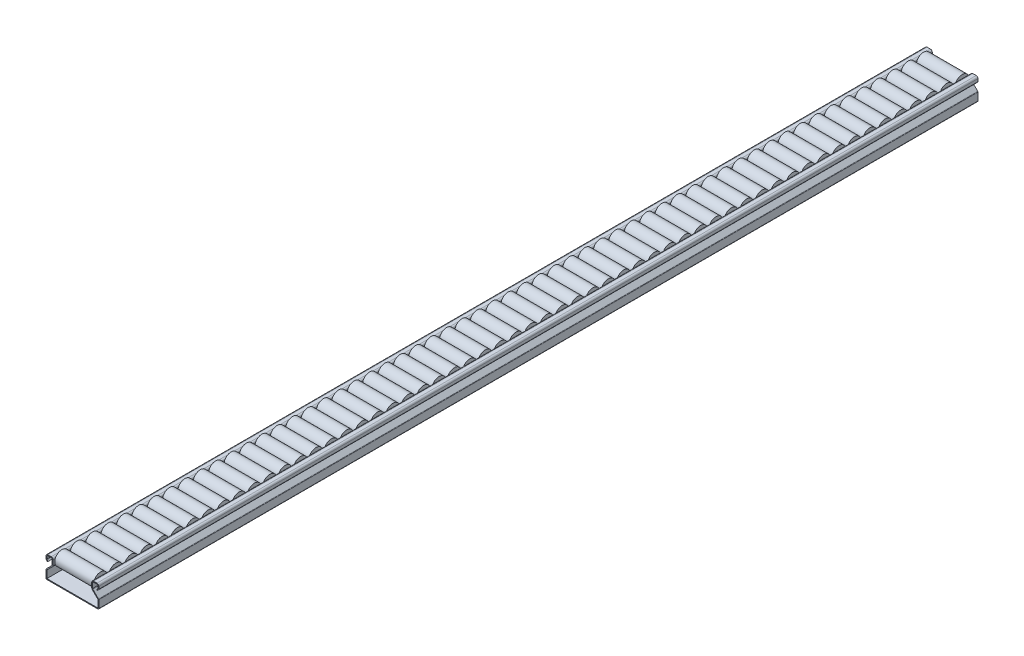
SolidWorks part; units mm, degrees
ref_plane "Front Plane" through (0, 0, 0) normal (0, 0, 1) x (1, 0, 0)
ref_plane "Top Plane" through (0, 0, 0) normal (0, 1, 0) x (1, 0, 0)
ref_plane "Right Plane" through (0, 0, 0) normal (1, 0, 0) x (0, 0, -1)
ref_plane "Plane1" through (0, 0, 1000) normal (0, 0, 1) x (1, 0, 0)
sketch "Sketch1" plane through (0, 0, 1000) normal (0, 0, 1) x (1, 0, 0)
  line L0 (30, 0) -> (30, 25)
  line L1 (30, 25) -> (24, 25)
  line L2 (22, 23) -> (22, 17.4142)
  line L3 (22.5858, 16) -> (29, 9.5858)
  line L4 (29, 9.5858) -> (29, 1)
  line L5 (29, 1) -> (-29, 1)
  line L6 (-29, 1) -> (-29, 9.5858)
  line L7 (-29, 9.5858) -> (-22.5858, 16)
  line L8 (-22, 17.4142) -> (-22, 23)
  line L9 (-24, 25) -> (-30, 25)
  line L10 (-30, 25) -> (-30, 0)
  line L11 (-30, 0) -> (30, 0)
  arc A0 (24, 25) -> (22, 23) centre (24, 23) ccw
  arc A1 (22, 17.4142) -> (22.5858, 16) centre (24, 17.4142) ccw
  arc A2 (-22.5858, 16) -> (-22, 17.4142) centre (-24, 17.4142) ccw
  arc A3 (-22, 23) -> (-24, 25) centre (-24, 23) ccw
extrude "Boss-Extrude1" add sketch "Sketch1" against normal blind 1000
sketch "Sketch2" plane through (0, 0, 0) normal (0, 0, -1) x (-1, 0, 0)
  line L0 (30, 10) -> (30, 19.5858)
  line L1 (30, 19.5858) -> (28.2929, 17.8787)
  line L2 (28.2929, 17.8787) -> (27.5858, 18.5858)
  line L3 (27.5858, 18.5858) -> (29, 20)
  line L4 (29, 20) -> (29, 24)
  line L5 (29, 24) -> (23, 24)
  line L6 (23, 24) -> (23, 17)
  line L7 (23, 17) -> (30, 10)
extrude "Cut-Extrude1" cut sketch "Sketch2" against normal through all
sketch "Sketch3" plane through (0, 0, 0) normal (0, 0, -1) x (-1, 0, 0)
  line L0 (-30, 19.5858) -> (-30, 10)
  line L1 (-30, 10) -> (-23, 17)
  line L2 (-23, 17) -> (-23, 24)
  line L3 (-23, 24) -> (-29, 24)
  line L4 (-29, 24) -> (-29, 20)
  line L5 (-29, 20) -> (-27.5858, 18.5858)
  line L6 (-27.5858, 18.5858) -> (-28.2929, 17.8787)
  line L7 (-28.2929, 17.8787) -> (-30, 19.5858)
extrude "Cut-Extrude2" cut sketch "Sketch3" against normal through all
ref_plane "Plane2" through (0, 0, 10) normal (0, 0, -1) x (-1, 0, 0)
sketch "Sketch4" plane through (0, 0, 10) normal (0, 0, -1) x (-1, 0, 0)
  line L0 (-22, 28) -> (-22, 20)
  line L1 (-22, 20) -> (22, 20)
  line L2 (22, 20) -> (22, 28)
  line L3 (22, 28) -> (-22, 28)
  line L4 (-22, 20) -> (22, 20) construction
revolve "Revolve1" add sketch "Sketch4" angle 360 about L4 reverse direction yes
ref_plane "Plane3" through (0, 0, 990) normal (0, 0, -1) x (-1, 0, 0)
sketch "Sketch5" plane through (0, 0, 990) normal (0, 0, -1) x (-1, 0, 0)
  line L0 (-22, 28) -> (-22, 20)
  line L1 (-22, 20) -> (22, 20)
  line L2 (22, 20) -> (22, 28)
  line L3 (22, 28) -> (-22, 28)
  line L4 (-22, 20) -> (22, 20) construction
revolve "Revolve2" add sketch "Sketch5" angle 360 about L4 reverse direction yes
ref_plane "Plane4" through (0, 0, 27.5) normal (0, 0, -1) x (-1, 0, 0)
sketch "Sketch6" plane through (0, 0, 27.5) normal (0, 0, -1) x (-1, 0, 0)
  line L0 (-22, 28) -> (-22, 20)
  line L1 (-22, 20) -> (22, 20)
  line L2 (22, 20) -> (22, 28)
  line L3 (22, 28) -> (-22, 28)
  line L4 (-22, 20) -> (22, 20) construction
revolve "Revolve3" add sketch "Sketch6" angle 360 about L4 reverse direction yes
ref_plane "Plane5" through (0, 0, 45) normal (0, 0, -1) x (-1, 0, 0)
sketch "Sketch7" plane through (0, 0, 45) normal (0, 0, -1) x (-1, 0, 0)
  line L0 (-22, 28) -> (-22, 20)
  line L1 (-22, 20) -> (22, 20)
  line L2 (22, 20) -> (22, 28)
  line L3 (22, 28) -> (-22, 28)
  line L4 (-22, 20) -> (22, 20) construction
revolve "Revolve4" add sketch "Sketch7" angle 360 about L4 reverse direction yes
ref_plane "Plane6" through (0, 0, 62.5) normal (0, 0, -1) x (-1, 0, 0)
sketch "Sketch8" plane through (0, 0, 62.5) normal (0, 0, -1) x (-1, 0, 0)
  line L0 (-22, 28) -> (-22, 20)
  line L1 (-22, 20) -> (22, 20)
  line L2 (22, 20) -> (22, 28)
  line L3 (22, 28) -> (-22, 28)
  line L4 (-22, 20) -> (22, 20) construction
revolve "Revolve5" add sketch "Sketch8" angle 360 about L4 reverse direction yes
ref_plane "Plane7" through (0, 0, 80) normal (0, 0, -1) x (-1, 0, 0)
sketch "Sketch9" plane through (0, 0, 80) normal (0, 0, -1) x (-1, 0, 0)
  line L0 (-22, 28) -> (-22, 20)
  line L1 (-22, 20) -> (22, 20)
  line L2 (22, 20) -> (22, 28)
  line L3 (22, 28) -> (-22, 28)
  line L4 (-22, 20) -> (22, 20) construction
revolve "Revolve6" add sketch "Sketch9" angle 360 about L4 reverse direction yes
ref_plane "Plane8" through (0, 0, 97.5) normal (0, 0, -1) x (-1, 0, 0)
sketch "Sketch10" plane through (0, 0, 97.5) normal (0, 0, -1) x (-1, 0, 0)
  line L0 (-22, 28) -> (-22, 20)
  line L1 (-22, 20) -> (22, 20)
  line L2 (22, 20) -> (22, 28)
  line L3 (22, 28) -> (-22, 28)
  line L4 (-22, 20) -> (22, 20) construction
revolve "Revolve7" add sketch "Sketch10" angle 360 about L4 reverse direction yes
ref_plane "Plane9" through (0, 0, 115) normal (0, 0, -1) x (-1, 0, 0)
sketch "Sketch11" plane through (0, 0, 115) normal (0, 0, -1) x (-1, 0, 0)
  line L0 (-22, 28) -> (-22, 20)
  line L1 (-22, 20) -> (22, 20)
  line L2 (22, 20) -> (22, 28)
  line L3 (22, 28) -> (-22, 28)
  line L4 (-22, 20) -> (22, 20) construction
revolve "Revolve8" add sketch "Sketch11" angle 360 about L4 reverse direction yes
ref_plane "Plane10" through (0, 0, 132.5) normal (0, 0, -1) x (-1, 0, 0)
sketch "Sketch12" plane through (0, 0, 132.5) normal (0, 0, -1) x (-1, 0, 0)
  line L0 (-22, 28) -> (-22, 20)
  line L1 (-22, 20) -> (22, 20)
  line L2 (22, 20) -> (22, 28)
  line L3 (22, 28) -> (-22, 28)
  line L4 (-22, 20) -> (22, 20) construction
revolve "Revolve9" add sketch "Sketch12" angle 360 about L4 reverse direction yes
ref_plane "Plane11" through (0, 0, 150) normal (0, 0, -1) x (-1, 0, 0)
sketch "Sketch13" plane through (0, 0, 150) normal (0, 0, -1) x (-1, 0, 0)
  line L0 (-22, 28) -> (-22, 20)
  line L1 (-22, 20) -> (22, 20)
  line L2 (22, 20) -> (22, 28)
  line L3 (22, 28) -> (-22, 28)
  line L4 (-22, 20) -> (22, 20) construction
revolve "Revolve10" add sketch "Sketch13" angle 360 about L4 reverse direction yes
ref_plane "Plane12" through (0, 0, 167.5) normal (0, 0, -1) x (-1, 0, 0)
sketch "Sketch14" plane through (0, 0, 167.5) normal (0, 0, -1) x (-1, 0, 0)
  line L0 (-22, 28) -> (-22, 20)
  line L1 (-22, 20) -> (22, 20)
  line L2 (22, 20) -> (22, 28)
  line L3 (22, 28) -> (-22, 28)
  line L4 (-22, 20) -> (22, 20) construction
revolve "Revolve11" add sketch "Sketch14" angle 360 about L4 reverse direction yes
ref_plane "Plane13" through (0, 0, 185) normal (0, 0, -1) x (-1, 0, 0)
sketch "Sketch15" plane through (0, 0, 185) normal (0, 0, -1) x (-1, 0, 0)
  line L0 (-22, 28) -> (-22, 20)
  line L1 (-22, 20) -> (22, 20)
  line L2 (22, 20) -> (22, 28)
  line L3 (22, 28) -> (-22, 28)
  line L4 (-22, 20) -> (22, 20) construction
revolve "Revolve12" add sketch "Sketch15" angle 360 about L4 reverse direction yes
ref_plane "Plane14" through (0, 0, 202.5) normal (0, 0, -1) x (-1, 0, 0)
sketch "Sketch16" plane through (0, 0, 202.5) normal (0, 0, -1) x (-1, 0, 0)
  line L0 (-22, 28) -> (-22, 20)
  line L1 (-22, 20) -> (22, 20)
  line L2 (22, 20) -> (22, 28)
  line L3 (22, 28) -> (-22, 28)
  line L4 (-22, 20) -> (22, 20) construction
revolve "Revolve13" add sketch "Sketch16" angle 360 about L4 reverse direction yes
ref_plane "Plane15" through (0, 0, 220) normal (0, 0, -1) x (-1, 0, 0)
sketch "Sketch17" plane through (0, 0, 220) normal (0, 0, -1) x (-1, 0, 0)
  line L0 (-22, 28) -> (-22, 20)
  line L1 (-22, 20) -> (22, 20)
  line L2 (22, 20) -> (22, 28)
  line L3 (22, 28) -> (-22, 28)
  line L4 (-22, 20) -> (22, 20) construction
revolve "Revolve14" add sketch "Sketch17" angle 360 about L4 reverse direction yes
ref_plane "Plane16" through (0, 0, 237.5) normal (0, 0, -1) x (-1, 0, 0)
sketch "Sketch18" plane through (0, 0, 237.5) normal (0, 0, -1) x (-1, 0, 0)
  line L0 (-22, 28) -> (-22, 20)
  line L1 (-22, 20) -> (22, 20)
  line L2 (22, 20) -> (22, 28)
  line L3 (22, 28) -> (-22, 28)
  line L4 (-22, 20) -> (22, 20) construction
revolve "Revolve15" add sketch "Sketch18" angle 360 about L4 reverse direction yes
ref_plane "Plane17" through (0, 0, 255) normal (0, 0, -1) x (-1, 0, 0)
sketch "Sketch19" plane through (0, 0, 255) normal (0, 0, -1) x (-1, 0, 0)
  line L0 (-22, 28) -> (-22, 20)
  line L1 (-22, 20) -> (22, 20)
  line L2 (22, 20) -> (22, 28)
  line L3 (22, 28) -> (-22, 28)
  line L4 (-22, 20) -> (22, 20) construction
revolve "Revolve16" add sketch "Sketch19" angle 360 about L4 reverse direction yes
ref_plane "Plane18" through (0, 0, 272.5) normal (0, 0, -1) x (-1, 0, 0)
sketch "Sketch20" plane through (0, 0, 272.5) normal (0, 0, -1) x (-1, 0, 0)
  line L0 (-22, 28) -> (-22, 20)
  line L1 (-22, 20) -> (22, 20)
  line L2 (22, 20) -> (22, 28)
  line L3 (22, 28) -> (-22, 28)
  line L4 (-22, 20) -> (22, 20) construction
revolve "Revolve17" add sketch "Sketch20" angle 360 about L4 reverse direction yes
ref_plane "Plane19" through (0, 0, 290) normal (0, 0, -1) x (-1, 0, 0)
sketch "Sketch21" plane through (0, 0, 290) normal (0, 0, -1) x (-1, 0, 0)
  line L0 (-22, 28) -> (-22, 20)
  line L1 (-22, 20) -> (22, 20)
  line L2 (22, 20) -> (22, 28)
  line L3 (22, 28) -> (-22, 28)
  line L4 (-22, 20) -> (22, 20) construction
revolve "Revolve18" add sketch "Sketch21" angle 360 about L4 reverse direction yes
ref_plane "Plane20" through (0, 0, 307.5) normal (0, 0, -1) x (-1, 0, 0)
sketch "Sketch22" plane through (0, 0, 307.5) normal (0, 0, -1) x (-1, 0, 0)
  line L0 (-22, 28) -> (-22, 20)
  line L1 (-22, 20) -> (22, 20)
  line L2 (22, 20) -> (22, 28)
  line L3 (22, 28) -> (-22, 28)
  line L4 (-22, 20) -> (22, 20) construction
revolve "Revolve19" add sketch "Sketch22" angle 360 about L4 reverse direction yes
ref_plane "Plane21" through (0, 0, 325) normal (0, 0, -1) x (-1, 0, 0)
sketch "Sketch23" plane through (0, 0, 325) normal (0, 0, -1) x (-1, 0, 0)
  line L0 (-22, 28) -> (-22, 20)
  line L1 (-22, 20) -> (22, 20)
  line L2 (22, 20) -> (22, 28)
  line L3 (22, 28) -> (-22, 28)
  line L4 (-22, 20) -> (22, 20) construction
revolve "Revolve20" add sketch "Sketch23" angle 360 about L4 reverse direction yes
ref_plane "Plane22" through (0, 0, 342.5) normal (0, 0, -1) x (-1, 0, 0)
sketch "Sketch24" plane through (0, 0, 342.5) normal (0, 0, -1) x (-1, 0, 0)
  line L0 (-22, 28) -> (-22, 20)
  line L1 (-22, 20) -> (22, 20)
  line L2 (22, 20) -> (22, 28)
  line L3 (22, 28) -> (-22, 28)
  line L4 (-22, 20) -> (22, 20) construction
revolve "Revolve21" add sketch "Sketch24" angle 360 about L4 reverse direction yes
ref_plane "Plane23" through (0, 0, 360) normal (0, 0, -1) x (-1, 0, 0)
sketch "Sketch25" plane through (0, 0, 360) normal (0, 0, -1) x (-1, 0, 0)
  line L0 (-22, 28) -> (-22, 20)
  line L1 (-22, 20) -> (22, 20)
  line L2 (22, 20) -> (22, 28)
  line L3 (22, 28) -> (-22, 28)
  line L4 (-22, 20) -> (22, 20) construction
revolve "Revolve22" add sketch "Sketch25" angle 360 about L4 reverse direction yes
ref_plane "Plane24" through (0, 0, 377.5) normal (0, 0, -1) x (-1, 0, 0)
sketch "Sketch26" plane through (0, 0, 377.5) normal (0, 0, -1) x (-1, 0, 0)
  line L0 (-22, 28) -> (-22, 20)
  line L1 (-22, 20) -> (22, 20)
  line L2 (22, 20) -> (22, 28)
  line L3 (22, 28) -> (-22, 28)
  line L4 (-22, 20) -> (22, 20) construction
revolve "Revolve23" add sketch "Sketch26" angle 360 about L4 reverse direction yes
ref_plane "Plane25" through (0, 0, 395) normal (0, 0, -1) x (-1, 0, 0)
sketch "Sketch27" plane through (0, 0, 395) normal (0, 0, -1) x (-1, 0, 0)
  line L0 (-22, 28) -> (-22, 20)
  line L1 (-22, 20) -> (22, 20)
  line L2 (22, 20) -> (22, 28)
  line L3 (22, 28) -> (-22, 28)
  line L4 (-22, 20) -> (22, 20) construction
revolve "Revolve24" add sketch "Sketch27" angle 360 about L4 reverse direction yes
ref_plane "Plane26" through (0, 0, 412.5) normal (0, 0, -1) x (-1, 0, 0)
sketch "Sketch28" plane through (0, 0, 412.5) normal (0, 0, -1) x (-1, 0, 0)
  line L0 (-22, 28) -> (-22, 20)
  line L1 (-22, 20) -> (22, 20)
  line L2 (22, 20) -> (22, 28)
  line L3 (22, 28) -> (-22, 28)
  line L4 (-22, 20) -> (22, 20) construction
revolve "Revolve25" add sketch "Sketch28" angle 360 about L4 reverse direction yes
ref_plane "Plane27" through (0, 0, 430) normal (0, 0, -1) x (-1, 0, 0)
sketch "Sketch29" plane through (0, 0, 430) normal (0, 0, -1) x (-1, 0, 0)
  line L0 (-22, 28) -> (-22, 20)
  line L1 (-22, 20) -> (22, 20)
  line L2 (22, 20) -> (22, 28)
  line L3 (22, 28) -> (-22, 28)
  line L4 (-22, 20) -> (22, 20) construction
revolve "Revolve26" add sketch "Sketch29" angle 360 about L4 reverse direction yes
ref_plane "Plane28" through (0, 0, 447.5) normal (0, 0, -1) x (-1, 0, 0)
sketch "Sketch30" plane through (0, 0, 447.5) normal (0, 0, -1) x (-1, 0, 0)
  line L0 (-22, 28) -> (-22, 20)
  line L1 (-22, 20) -> (22, 20)
  line L2 (22, 20) -> (22, 28)
  line L3 (22, 28) -> (-22, 28)
  line L4 (-22, 20) -> (22, 20) construction
revolve "Revolve27" add sketch "Sketch30" angle 360 about L4 reverse direction yes
ref_plane "Plane29" through (0, 0, 465) normal (0, 0, -1) x (-1, 0, 0)
sketch "Sketch31" plane through (0, 0, 465) normal (0, 0, -1) x (-1, 0, 0)
  line L0 (-22, 28) -> (-22, 20)
  line L1 (-22, 20) -> (22, 20)
  line L2 (22, 20) -> (22, 28)
  line L3 (22, 28) -> (-22, 28)
  line L4 (-22, 20) -> (22, 20) construction
revolve "Revolve28" add sketch "Sketch31" angle 360 about L4 reverse direction yes
ref_plane "Plane30" through (0, 0, 482.5) normal (0, 0, -1) x (-1, 0, 0)
sketch "Sketch32" plane through (0, 0, 482.5) normal (0, 0, -1) x (-1, 0, 0)
  line L0 (-22, 28) -> (-22, 20)
  line L1 (-22, 20) -> (22, 20)
  line L2 (22, 20) -> (22, 28)
  line L3 (22, 28) -> (-22, 28)
  line L4 (-22, 20) -> (22, 20) construction
revolve "Revolve29" add sketch "Sketch32" angle 360 about L4 reverse direction yes
ref_plane "Plane31" through (0, 0, 500) normal (0, 0, -1) x (-1, 0, 0)
sketch "Sketch33" plane through (0, 0, 500) normal (0, 0, -1) x (-1, 0, 0)
  line L0 (-22, 28) -> (-22, 20)
  line L1 (-22, 20) -> (22, 20)
  line L2 (22, 20) -> (22, 28)
  line L3 (22, 28) -> (-22, 28)
  line L4 (-22, 20) -> (22, 20) construction
revolve "Revolve30" add sketch "Sketch33" angle 360 about L4 reverse direction yes
ref_plane "Plane32" through (0, 0, 517.5) normal (0, 0, -1) x (-1, 0, 0)
sketch "Sketch34" plane through (0, 0, 517.5) normal (0, 0, -1) x (-1, 0, 0)
  line L0 (-22, 28) -> (-22, 20)
  line L1 (-22, 20) -> (22, 20)
  line L2 (22, 20) -> (22, 28)
  line L3 (22, 28) -> (-22, 28)
  line L4 (-22, 20) -> (22, 20) construction
revolve "Revolve31" add sketch "Sketch34" angle 360 about L4 reverse direction yes
ref_plane "Plane33" through (0, 0, 535) normal (0, 0, -1) x (-1, 0, 0)
sketch "Sketch35" plane through (0, 0, 535) normal (0, 0, -1) x (-1, 0, 0)
  line L0 (-22, 28) -> (-22, 20)
  line L1 (-22, 20) -> (22, 20)
  line L2 (22, 20) -> (22, 28)
  line L3 (22, 28) -> (-22, 28)
  line L4 (-22, 20) -> (22, 20) construction
revolve "Revolve32" add sketch "Sketch35" angle 360 about L4 reverse direction yes
ref_plane "Plane34" through (0, 0, 552.5) normal (0, 0, -1) x (-1, 0, 0)
sketch "Sketch36" plane through (0, 0, 552.5) normal (0, 0, -1) x (-1, 0, 0)
  line L0 (-22, 28) -> (-22, 20)
  line L1 (-22, 20) -> (22, 20)
  line L2 (22, 20) -> (22, 28)
  line L3 (22, 28) -> (-22, 28)
  line L4 (-22, 20) -> (22, 20) construction
revolve "Revolve33" add sketch "Sketch36" angle 360 about L4 reverse direction yes
ref_plane "Plane35" through (0, 0, 570) normal (0, 0, -1) x (-1, 0, 0)
sketch "Sketch37" plane through (0, 0, 570) normal (0, 0, -1) x (-1, 0, 0)
  line L0 (-22, 28) -> (-22, 20)
  line L1 (-22, 20) -> (22, 20)
  line L2 (22, 20) -> (22, 28)
  line L3 (22, 28) -> (-22, 28)
  line L4 (-22, 20) -> (22, 20) construction
revolve "Revolve34" add sketch "Sketch37" angle 360 about L4 reverse direction yes
ref_plane "Plane36" through (0, 0, 587.5) normal (0, 0, -1) x (-1, 0, 0)
sketch "Sketch38" plane through (0, 0, 587.5) normal (0, 0, -1) x (-1, 0, 0)
  line L0 (-22, 28) -> (-22, 20)
  line L1 (-22, 20) -> (22, 20)
  line L2 (22, 20) -> (22, 28)
  line L3 (22, 28) -> (-22, 28)
  line L4 (-22, 20) -> (22, 20) construction
revolve "Revolve35" add sketch "Sketch38" angle 360 about L4 reverse direction yes
ref_plane "Plane37" through (0, 0, 605) normal (0, 0, -1) x (-1, 0, 0)
sketch "Sketch39" plane through (0, 0, 605) normal (0, 0, -1) x (-1, 0, 0)
  line L0 (-22, 28) -> (-22, 20)
  line L1 (-22, 20) -> (22, 20)
  line L2 (22, 20) -> (22, 28)
  line L3 (22, 28) -> (-22, 28)
  line L4 (-22, 20) -> (22, 20) construction
revolve "Revolve36" add sketch "Sketch39" angle 360 about L4 reverse direction yes
ref_plane "Plane38" through (0, 0, 622.5) normal (0, 0, -1) x (-1, 0, 0)
sketch "Sketch40" plane through (0, 0, 622.5) normal (0, 0, -1) x (-1, 0, 0)
  line L0 (-22, 28) -> (-22, 20)
  line L1 (-22, 20) -> (22, 20)
  line L2 (22, 20) -> (22, 28)
  line L3 (22, 28) -> (-22, 28)
  line L4 (-22, 20) -> (22, 20) construction
revolve "Revolve37" add sketch "Sketch40" angle 360 about L4 reverse direction yes
ref_plane "Plane39" through (0, 0, 640) normal (0, 0, -1) x (-1, 0, 0)
sketch "Sketch41" plane through (0, 0, 640) normal (0, 0, -1) x (-1, 0, 0)
  line L0 (-22, 28) -> (-22, 20)
  line L1 (-22, 20) -> (22, 20)
  line L2 (22, 20) -> (22, 28)
  line L3 (22, 28) -> (-22, 28)
  line L4 (-22, 20) -> (22, 20) construction
revolve "Revolve38" add sketch "Sketch41" angle 360 about L4 reverse direction yes
ref_plane "Plane40" through (0, 0, 657.5) normal (0, 0, -1) x (-1, 0, 0)
sketch "Sketch42" plane through (0, 0, 657.5) normal (0, 0, -1) x (-1, 0, 0)
  line L0 (-22, 28) -> (-22, 20)
  line L1 (-22, 20) -> (22, 20)
  line L2 (22, 20) -> (22, 28)
  line L3 (22, 28) -> (-22, 28)
  line L4 (-22, 20) -> (22, 20) construction
revolve "Revolve39" add sketch "Sketch42" angle 360 about L4 reverse direction yes
ref_plane "Plane41" through (0, 0, 675) normal (0, 0, -1) x (-1, 0, 0)
sketch "Sketch43" plane through (0, 0, 675) normal (0, 0, -1) x (-1, 0, 0)
  line L0 (-22, 28) -> (-22, 20)
  line L1 (-22, 20) -> (22, 20)
  line L2 (22, 20) -> (22, 28)
  line L3 (22, 28) -> (-22, 28)
  line L4 (-22, 20) -> (22, 20) construction
revolve "Revolve40" add sketch "Sketch43" angle 360 about L4 reverse direction yes
ref_plane "Plane42" through (0, 0, 692.5) normal (0, 0, -1) x (-1, 0, 0)
sketch "Sketch44" plane through (0, 0, 692.5) normal (0, 0, -1) x (-1, 0, 0)
  line L0 (-22, 28) -> (-22, 20)
  line L1 (-22, 20) -> (22, 20)
  line L2 (22, 20) -> (22, 28)
  line L3 (22, 28) -> (-22, 28)
  line L4 (-22, 20) -> (22, 20) construction
revolve "Revolve41" add sketch "Sketch44" angle 360 about L4 reverse direction yes
ref_plane "Plane43" through (0, 0, 710) normal (0, 0, -1) x (-1, 0, 0)
sketch "Sketch45" plane through (0, 0, 710) normal (0, 0, -1) x (-1, 0, 0)
  line L0 (-22, 28) -> (-22, 20)
  line L1 (-22, 20) -> (22, 20)
  line L2 (22, 20) -> (22, 28)
  line L3 (22, 28) -> (-22, 28)
  line L4 (-22, 20) -> (22, 20) construction
revolve "Revolve42" add sketch "Sketch45" angle 360 about L4 reverse direction yes
ref_plane "Plane44" through (0, 0, 727.5) normal (0, 0, -1) x (-1, 0, 0)
sketch "Sketch46" plane through (0, 0, 727.5) normal (0, 0, -1) x (-1, 0, 0)
  line L0 (-22, 28) -> (-22, 20)
  line L1 (-22, 20) -> (22, 20)
  line L2 (22, 20) -> (22, 28)
  line L3 (22, 28) -> (-22, 28)
  line L4 (-22, 20) -> (22, 20) construction
revolve "Revolve43" add sketch "Sketch46" angle 360 about L4 reverse direction yes
ref_plane "Plane45" through (0, 0, 745) normal (0, 0, -1) x (-1, 0, 0)
sketch "Sketch47" plane through (0, 0, 745) normal (0, 0, -1) x (-1, 0, 0)
  line L0 (-22, 28) -> (-22, 20)
  line L1 (-22, 20) -> (22, 20)
  line L2 (22, 20) -> (22, 28)
  line L3 (22, 28) -> (-22, 28)
  line L4 (-22, 20) -> (22, 20) construction
revolve "Revolve44" add sketch "Sketch47" angle 360 about L4 reverse direction yes
ref_plane "Plane46" through (0, 0, 762.5) normal (0, 0, -1) x (-1, 0, 0)
sketch "Sketch48" plane through (0, 0, 762.5) normal (0, 0, -1) x (-1, 0, 0)
  line L0 (-22, 28) -> (-22, 20)
  line L1 (-22, 20) -> (22, 20)
  line L2 (22, 20) -> (22, 28)
  line L3 (22, 28) -> (-22, 28)
  line L4 (-22, 20) -> (22, 20) construction
revolve "Revolve45" add sketch "Sketch48" angle 360 about L4 reverse direction yes
ref_plane "Plane47" through (0, 0, 780) normal (0, 0, -1) x (-1, 0, 0)
sketch "Sketch49" plane through (0, 0, 780) normal (0, 0, -1) x (-1, 0, 0)
  line L0 (-22, 28) -> (-22, 20)
  line L1 (-22, 20) -> (22, 20)
  line L2 (22, 20) -> (22, 28)
  line L3 (22, 28) -> (-22, 28)
  line L4 (-22, 20) -> (22, 20) construction
revolve "Revolve46" add sketch "Sketch49" angle 360 about L4 reverse direction yes
ref_plane "Plane48" through (0, 0, 797.5) normal (0, 0, -1) x (-1, 0, 0)
sketch "Sketch50" plane through (0, 0, 797.5) normal (0, 0, -1) x (-1, 0, 0)
  line L0 (-22, 28) -> (-22, 20)
  line L1 (-22, 20) -> (22, 20)
  line L2 (22, 20) -> (22, 28)
  line L3 (22, 28) -> (-22, 28)
  line L4 (-22, 20) -> (22, 20) construction
revolve "Revolve47" add sketch "Sketch50" angle 360 about L4 reverse direction yes
ref_plane "Plane49" through (0, 0, 815) normal (0, 0, -1) x (-1, 0, 0)
sketch "Sketch51" plane through (0, 0, 815) normal (0, 0, -1) x (-1, 0, 0)
  line L0 (-22, 28) -> (-22, 20)
  line L1 (-22, 20) -> (22, 20)
  line L2 (22, 20) -> (22, 28)
  line L3 (22, 28) -> (-22, 28)
  line L4 (-22, 20) -> (22, 20) construction
revolve "Revolve48" add sketch "Sketch51" angle 360 about L4 reverse direction yes
ref_plane "Plane50" through (0, 0, 832.5) normal (0, 0, -1) x (-1, 0, 0)
sketch "Sketch52" plane through (0, 0, 832.5) normal (0, 0, -1) x (-1, 0, 0)
  line L0 (-22, 28) -> (-22, 20)
  line L1 (-22, 20) -> (22, 20)
  line L2 (22, 20) -> (22, 28)
  line L3 (22, 28) -> (-22, 28)
  line L4 (-22, 20) -> (22, 20) construction
revolve "Revolve49" add sketch "Sketch52" angle 360 about L4 reverse direction yes
ref_plane "Plane51" through (0, 0, 850) normal (0, 0, -1) x (-1, 0, 0)
sketch "Sketch53" plane through (0, 0, 850) normal (0, 0, -1) x (-1, 0, 0)
  line L0 (-22, 28) -> (-22, 20)
  line L1 (-22, 20) -> (22, 20)
  line L2 (22, 20) -> (22, 28)
  line L3 (22, 28) -> (-22, 28)
  line L4 (-22, 20) -> (22, 20) construction
revolve "Revolve50" add sketch "Sketch53" angle 360 about L4 reverse direction yes
ref_plane "Plane52" through (0, 0, 867.5) normal (0, 0, -1) x (-1, 0, 0)
sketch "Sketch54" plane through (0, 0, 867.5) normal (0, 0, -1) x (-1, 0, 0)
  line L0 (-22, 28) -> (-22, 20)
  line L1 (-22, 20) -> (22, 20)
  line L2 (22, 20) -> (22, 28)
  line L3 (22, 28) -> (-22, 28)
  line L4 (-22, 20) -> (22, 20) construction
revolve "Revolve51" add sketch "Sketch54" angle 360 about L4 reverse direction yes
ref_plane "Plane53" through (0, 0, 885) normal (0, 0, -1) x (-1, 0, 0)
sketch "Sketch55" plane through (0, 0, 885) normal (0, 0, -1) x (-1, 0, 0)
  line L0 (-22, 28) -> (-22, 20)
  line L1 (-22, 20) -> (22, 20)
  line L2 (22, 20) -> (22, 28)
  line L3 (22, 28) -> (-22, 28)
  line L4 (-22, 20) -> (22, 20) construction
revolve "Revolve52" add sketch "Sketch55" angle 360 about L4 reverse direction yes
ref_plane "Plane54" through (0, 0, 902.5) normal (0, 0, -1) x (-1, 0, 0)
sketch "Sketch56" plane through (0, 0, 902.5) normal (0, 0, -1) x (-1, 0, 0)
  line L0 (-22, 28) -> (-22, 20)
  line L1 (-22, 20) -> (22, 20)
  line L2 (22, 20) -> (22, 28)
  line L3 (22, 28) -> (-22, 28)
  line L4 (-22, 20) -> (22, 20) construction
revolve "Revolve53" add sketch "Sketch56" angle 360 about L4 reverse direction yes
ref_plane "Plane55" through (0, 0, 920) normal (0, 0, -1) x (-1, 0, 0)
sketch "Sketch57" plane through (0, 0, 920) normal (0, 0, -1) x (-1, 0, 0)
  line L0 (-22, 28) -> (-22, 20)
  line L1 (-22, 20) -> (22, 20)
  line L2 (22, 20) -> (22, 28)
  line L3 (22, 28) -> (-22, 28)
  line L4 (-22, 20) -> (22, 20) construction
revolve "Revolve54" add sketch "Sketch57" angle 360 about L4 reverse direction yes
ref_plane "Plane56" through (0, 0, 937.5) normal (0, 0, -1) x (-1, 0, 0)
sketch "Sketch58" plane through (0, 0, 937.5) normal (0, 0, -1) x (-1, 0, 0)
  line L0 (-22, 28) -> (-22, 20)
  line L1 (-22, 20) -> (22, 20)
  line L2 (22, 20) -> (22, 28)
  line L3 (22, 28) -> (-22, 28)
  line L4 (-22, 20) -> (22, 20) construction
revolve "Revolve55" add sketch "Sketch58" angle 360 about L4 reverse direction yes
ref_plane "Plane57" through (0, 0, 955) normal (0, 0, -1) x (-1, 0, 0)
sketch "Sketch59" plane through (0, 0, 955) normal (0, 0, -1) x (-1, 0, 0)
  line L0 (-22, 28) -> (-22, 20)
  line L1 (-22, 20) -> (22, 20)
  line L2 (22, 20) -> (22, 28)
  line L3 (22, 28) -> (-22, 28)
  line L4 (-22, 20) -> (22, 20) construction
revolve "Revolve56" add sketch "Sketch59" angle 360 about L4 reverse direction yes
ref_plane "Plane58" through (0, 0, 972.5) normal (0, 0, -1) x (-1, 0, 0)
sketch "Sketch60" plane through (0, 0, 972.5) normal (0, 0, -1) x (-1, 0, 0)
  line L0 (-22, 28) -> (-22, 20)
  line L1 (-22, 20) -> (22, 20)
  line L2 (22, 20) -> (22, 28)
  line L3 (22, 28) -> (-22, 28)
  line L4 (-22, 20) -> (22, 20) construction
revolve "Revolve57" add sketch "Sketch60" angle 360 about L4 reverse direction yes
fillet "Fillet1" radius 1 14 edges at (23, 24, 500) (-23, 24, 500) (29, 20, 500) (30, 19.5858, 500) (-23, 17, 500) (23, 17, 500) (-30, 19.5858, 500) (29, 24, 500) (-29, 20, 500) (-29, 24, 500) (30, 0, 500) (30, 10, 500) (-30, 10, 500) (-30, 0, 500) tangent propagation no
fillet "Fillet2" radius 2 2 edges at (30, 25, 500) (-30, 25, 500) tangent propagation no
